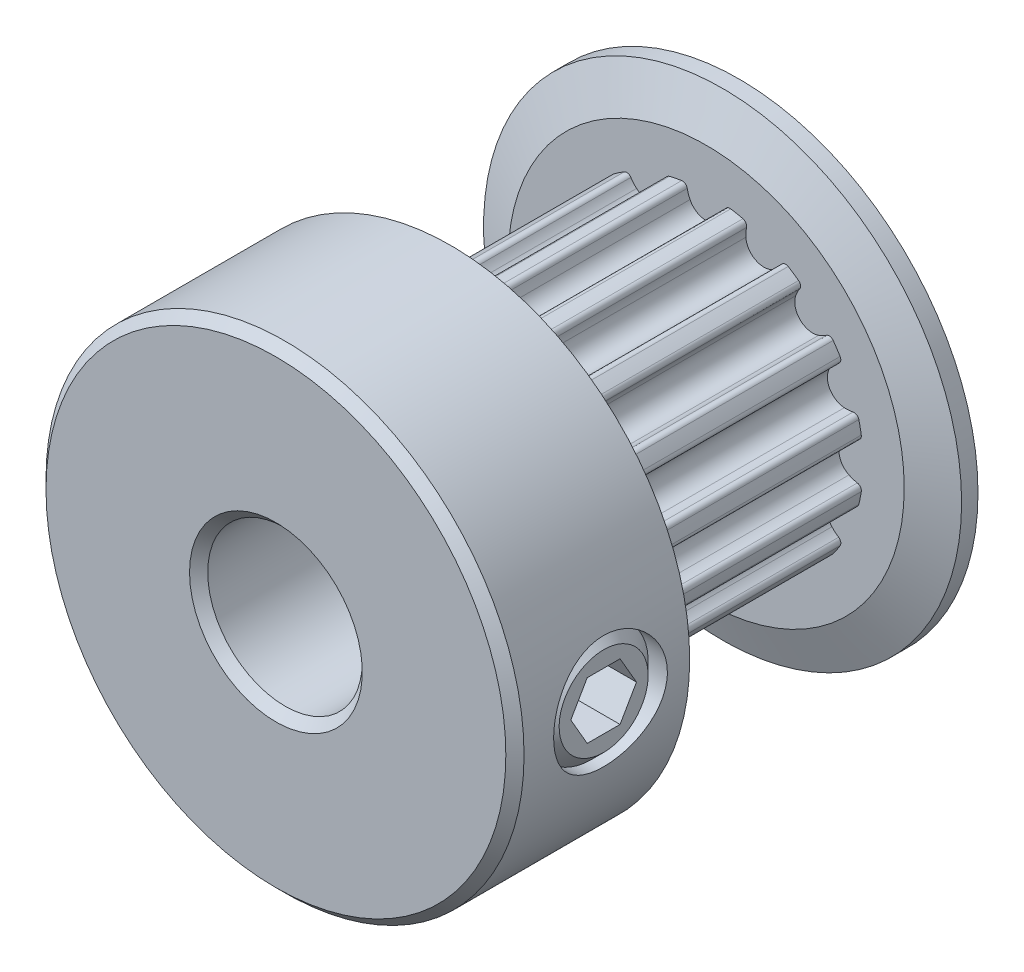
SolidWorks part; units mm, degrees
ref_plane "Front Plane" through (0, 0, 0) normal (0, 0, 1) x (1, 0, 0)
ref_plane "Top Plane" through (0, 0, 0) normal (0, 1, 0) x (1, 0, 0)
ref_plane "Right Plane" through (0, 0, 0) normal (1, 0, 0) x (0, 0, -1)
sketch "Sketch1" plane through (0, 0, 0) normal (0, 0, 1) x (1, 0, 0)
  line L1 (-1.706, 4.0885) -> (1.706, 4.0885) construction
  line L4 (0, 0) -> (0, 4.0885) construction
  line L5 (0, 4.0885) -> (0, 10.3909) construction
  line L6 (0, 5.0925) -> (1.9611, 4.6998) construction
  line L7 (1.9611, 4.6998) -> (2.5723, 4.4447) construction
  line L8 (1.9611, 4.6998) -> (1.706, 4.0885) construction
  line L9 (-1.9611, 4.6998) -> (-1.706, 4.0885) construction
  line L10 (-1.8632, 4.4654) -> (-3.0736, 7.366)
  line L11 (-3.0736, 7.366) -> (3.0736, 7.366)
  line L12 (3.0736, 7.366) -> (1.8632, 4.4654)
  circle A0 centre (0, 0) radius 5.0925 construction
  circle A1 centre (0, 0) radius 7.366 construction
  circle A2 centre (0, 0) radius 4.8385 construction
  arc A3 (-0.4989, 4.4003) -> (0.4989, 4.4003) centre (0, 4.6435) ccw
  arc A4 (-0.4989, 4.4003) -> (-0.5836, 4.6582) centre (0.4, 4.8385) cw
  arc A5 (-1.8632, 4.4654) -> (-0.7545, 4.7793) centre (0, 0) cw
  arc A6 (-0.5836, 4.6582) -> (-0.7545, 4.7793) centre (-0.7312, 4.6311) ccw
  arc A7 (1.8632, 4.4654) -> (0.7545, 4.7793) centre (0, 0) ccw
  arc A8 (0.5836, 4.6582) -> (0.7545, 4.7793) centre (0.7312, 4.6311) cw
  arc A9 (0.4989, 4.4003) -> (0.5836, 4.6582) centre (-0.4, 4.8385) ccw
  point P6 (0, 20.9083)
  point P11 (0, 5.0925)
  point P13 (0, 7.366)
  point P14 (0, 4.8385)
  dimension "D1" = 10.5174
  dimension "D2" = 5.2984
sketch "Sketch2" plane through (0, 0, 0) normal (1, 0, 0) x (0, 0, -1)
  line L0 (-7.135, 2.3812) -> (7.135, 2.3812)
  line L1 (-7.135, 2.3812) -> (-7.135, 7.366)
  line L2 (-1.75, 7.366) -> (-7.135, 7.366)
  line L3 (-2.255, 2.3813) -> (-2.255, 7.366) construction
  line L4 (-2.255, 7.366) -> (-1.245, 7.366) construction
  line L5 (-1.245, 7.366) -> (-1.245, 4.8385) construction
  line L6 (-1.245, 4.8385) -> (6.125, 4.8385)
  line L7 (6.125, 4.8385) -> (6.125, 7.366) construction
  line L8 (6.125, 7.366) -> (7.135, 7.366) construction
  line L9 (7.135, 7.366) -> (7.135, 2.3812)
  line L10 (-7.135, 0) -> (7.135, 0) construction
  line L11 (6.63, 7.366) -> (6.125, 6.1022)
  line L12 (-1.245, 6.1022) -> (-1.75, 7.366)
  line L14 (-1.245, 6.1022) -> (-1.245, 4.8385)
  line L15 (6.125, 4.8385) -> (6.125, 6.1022)
  line L16 (6.63, 7.366) -> (7.135, 7.366)
  arc A0 (-1.245, 6.1022) -> (-1.75, 7.366) centre (-3.0788, 6.1022) ccw construction
  arc A1 (6.125, 6.1022) -> (6.63, 7.366) centre (7.9588, 6.1022) cw construction
  point P12 (-1.245, 6.1022)
  point P14 (-1.75, 7.366)
  point P20 (6.125, 6.1022)
  point P21 (6.63, 7.366)
  point P25 (6.125, 0)
  point P26 (-1.245, 0)
  dimension "OA" = 14.27
  dimension "Bore" = 4.7625
  dimension "Outside Width" = 8.38
  dimension "Inside Width" = 7.37
revolve "Revolve1" add sketch "Sketch2" angle 360 mid plane about L10
sketch "Sketch3" plane through (0, 0, 0) normal (0, 0, 1) x (1, 0, 0)
  line L6 (3.0736, 7.366) -> (-3.0736, 7.366)
  line L7 (1.8632, 4.4654) -> (3.0736, 7.366)
  line L8 (-3.0736, 7.366) -> (-1.8632, 4.4654)
  line L9 (3.0736, 7.366) -> (-3.0736, 7.366)
  line L10 (1.8632, 4.4654) -> (3.0736, 7.366)
  line L11 (-3.0736, 7.366) -> (-1.8632, 4.4654)
  arc A8 (1.8632, 4.4654) -> (0.7545, 4.7793) centre (0, 0) ccw
  arc A9 (0.7545, 4.7793) -> (0.5836, 4.6582) centre (0.7312, 4.6311) ccw
  arc A10 (0.4989, 4.4003) -> (0.5836, 4.6582) centre (-0.4, 4.8385) ccw
  arc A11 (-0.4989, 4.4003) -> (0.4989, 4.4003) centre (0, 4.6435) ccw
  arc A12 (-0.5836, 4.6582) -> (-0.4989, 4.4003) centre (0.4, 4.8385) ccw
  arc A13 (-0.5836, 4.6582) -> (-0.7545, 4.7793) centre (-0.7312, 4.6311) ccw
  arc A14 (-0.7545, 4.7793) -> (-1.8632, 4.4654) centre (0, 0) ccw
  arc A15 (1.8632, 4.4654) -> (0.7545, 4.7793) centre (0, 0) ccw
  arc A16 (0.7545, 4.7793) -> (0.5836, 4.6582) centre (0.7312, 4.6311) ccw
  arc A17 (0.4989, 4.4003) -> (0.5836, 4.6582) centre (-0.4, 4.8385) ccw
  arc A18 (-0.4989, 4.4003) -> (0.4989, 4.4003) centre (0, 4.6435) ccw
  arc A19 (-0.5836, 4.6582) -> (-0.4989, 4.4003) centre (0.4, 4.8385) ccw
  arc A20 (-0.5836, 4.6582) -> (-0.7545, 4.7793) centre (-0.7312, 4.6311) ccw
  arc A21 (-0.7545, 4.7793) -> (-1.8632, 4.4654) centre (0, 0) ccw
  dimension "D1" = 0
extrude "Cut-Extrude1" cut sketch "Sketch3" against normal up to vertex (6.125 mm away) from vertex up to point (0, 4.8385, -6.125) starting at point (0, 4.8385, 1.245)
pattern_circular "CirPattern1" count 16 over 360 about axis through (0, 0, 7.135) along (0, 0, 1) of "Cut-Extrude1"
sketch "Sketch4" plane through (0, 0, 0) normal (1, 0, 0) x (0, -1, 0)
  line L0 (0, -1.245) -> (0, -7.135) construction
  line L1 (-2.3812, -7.135) -> (2.3812, -7.135) construction
  line L2 (6.1022, -1.245) -> (-6.1022, -1.245) construction
  circle A0 centre (0, -4.19) radius 1.7526
extrude "Cut-Extrude2" cut sketch "Sketch4" along normal through all
ref_plane "Plane1" through (0, 0, 4.19) normal (0, 0, 1) x (1, 0, 0)
sketch "Sketch5" plane through (0, 0, 4.19) normal (0, 0, 1) x (1, 0, 0)
  line L0 (0, 0) -> (0, 7.366) construction
  line L1 (2.3812, -1.3716) -> (2.3812, 0)
  line L2 (2.7622, -1.7526) -> (6.7735, -1.7526)
  line L3 (2.3812, 0) -> (7.366, 0) construction
  line L4 (2.3812, 0) -> (7.1545, 0)
  line L5 (7.1545, 0) -> (7.1545, -1.3716)
  line L6 (2.7622, -1.7526) -> (2.3812, -1.3716)
  line L7 (7.1545, -1.3716) -> (6.7735, -1.7526)
  circle A0 centre (0, 0) radius 7.366 construction
  circle A1 centre (0, 0) radius 2.3812 construction
  point P2 (2.3812, -1.7526)
  point P11 (7.1545, -1.7526)
revolve "Revolve2" add sketch "Sketch5" angle 360 mid plane about L4
sketch "Sketch6" plane through (7.1545, 5.3841, 0) normal (-1, 0, 0) x (0, -1, 0)
  line L1 (5.3841, 5.2019) -> (4.5078, 4.6959)
  line L2 (4.5078, 4.6959) -> (4.5078, 3.6841)
  line L3 (4.5078, 3.6841) -> (5.3841, 3.1781)
  line L4 (5.3841, 3.1781) -> (6.2604, 3.6841)
  line L5 (6.2604, 3.6841) -> (6.2604, 4.6959)
  line L6 (6.2604, 4.6959) -> (5.3841, 5.2019)
  circle A0 centre (5.3841, 4.19) radius 0.8763 construction
  dimension "D1" = 1.7526
extrude "Cut-Extrude3" cut sketch "Sketch6" along normal blind 1.3144
chamfer "Chamfer1" distance 0.2807 angle 45 2 edges at (2.3812, 0, 7.135) (7.366, 0, 7.135)
ref_axis "Center Axis 1" through (0, 0, -7.135) along (0, 0, 1)
ref_plane "Contact Plane 1" through (0, 0, 7.135) normal (0, 0, 1) x (1, 0, 0)
ref_plane "Contact Plane 2" through (0, 0, -7.135) normal (0, 0, -1) x (-1, 0, 0)
equation "\"D2@Sketch1\"= \"D1@Sketch1\" / 2"
equation "\"D1@Sketch6\" = \"Set Screw@Sketch4\" / 2"
equation "\"D1@Cut-Extrude3\" = \"D1@Sketch6\"*.75"
